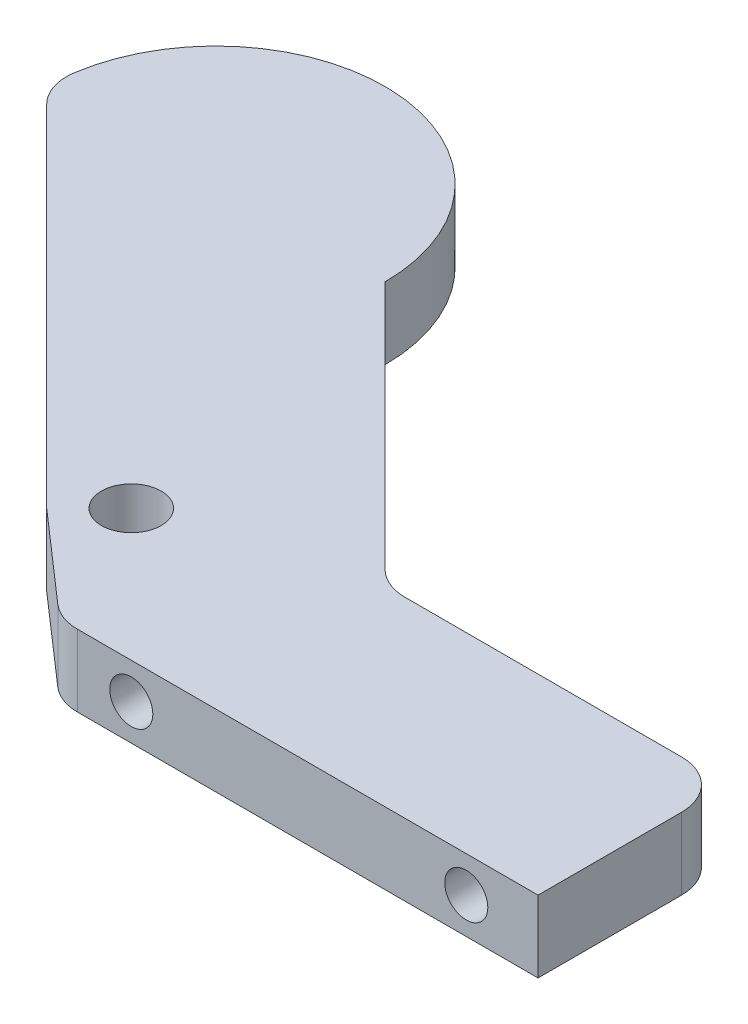
SolidWorks part; units mm, degrees
ref_plane "Front Plane" through (0, 0, 0) normal (0, 0, 1) x (1, 0, 0)
ref_plane "Top Plane" through (0, 0, 0) normal (0, 1, 0) x (1, 0, 0)
ref_plane "Right Plane" through (0, 0, 0) normal (1, 0, 0) x (0, 0, -1)
sketch "Sketch1" plane through (0, 0, 0) normal (0, 1, 0) x (1, 0, 0)
  line L0 (0, 6.35) -> (12.3665, 6.35)
  line L1 (12.3665, 6.35) -> (57.15, 6.35)
  line L2 (6.35, 0) -> (6.35, -13.97)
  line L3 (6.35, -13.97) -> (57.15, -13.97)
  line L4 (57.15, 6.35) -> (57.15, -13.97)
  line L5 (20.5908, 6.35) -> (-7.3492, 34.29)
  line L6 (-4.4901, -4.4901) -> (-43.2703, 34.29)
  line L7 (-4.4901, -4.4901) -> (6.35, -13.97)
  circle A0 centre (0, 0) radius 3.175
  arc A1 (0, 6.35) -> (6.35, 0) centre (0, 0) ccw
  arc A2 (-43.2703, 34.29) -> (-7.3492, 34.29) centre (-25.3097, 34.29) cw
  dimension "D1" = 12.7
  dimension "D2" = 6.35
  dimension "D3" = 6.35
  dimension "D4" = 50.8
  dimension "D5" = 20.32
  dimension "D6" = 45
  dimension "D7" = 25.4
  dimension "D8" = 27.94
extrude "Boss-Extrude1" add sketch "Sketch1" along normal mid plane 7.62 contours A2 L6 A1 L0 L1 L5 | L0 A1 L2 L3 L4 L1 A0 | A1 L7 L2 region at (-15.7867, 0, -26.7963) region at (28.8904, 0, 3.4247) region at (3.6646, 0, 8.0416)
sketch "Sketch2" plane through (0, 0, 13.97) normal (0, 0, 1) x (1, 0, 0)
  circle A0 centre (49.53, 0) radius 2.5908 construction
  circle A1 centre (13.97, 0) radius 2.5908 construction
  circle A2 centre (49.53, 0) radius 2.5908
  circle A3 centre (13.97, 0) radius 2.5908
  circle A4 centre (13.97, 0) radius 2.286
  circle A5 centre (49.53, 0) radius 2.286
  dimension "D1" = 4.572
  dimension "D2" = 4.572
extrude "Cut-Extrude1" cut sketch "Sketch2" against normal blind 5.08 contours A4 | A5 region at (13.97, 0, 13.97) region at (49.53, 0, 13.97)
fillet "Fillet1" radius 5.08 4 edges at (57.15, 0, -6.35) (20.5908, 0, -6.35) (6.35, 0, 13.97) (-43.2703, 0, -34.29)
